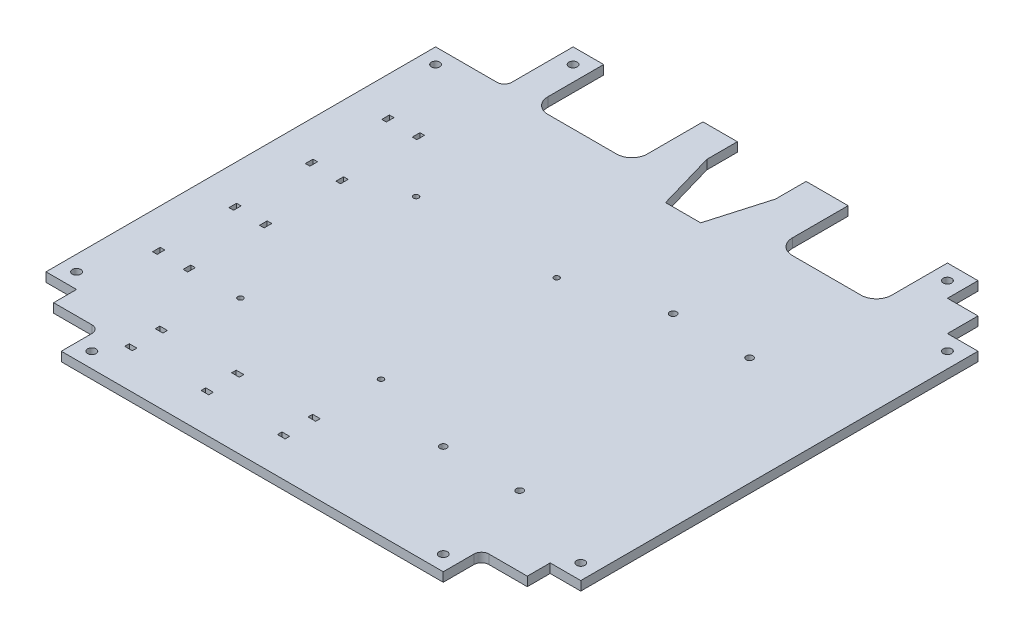
SolidWorks part; units mm, degrees
material "ABS PC"
ref_plane "Front Plane" through (0, 0, 0) normal (0, 0, 1) x (1, 0, 0)
ref_plane "Top Plane" through (0, 0, 0) normal (0, 1, 0) x (1, 0, 0)
ref_plane "Right Plane" through (0, 0, 0) normal (1, 0, 0) x (0, 0, -1)
sketch "Sketch1" plane through (0, 0, 0) normal (0, 1, 0) x (1, 0, 0)
  line L1 (-175, -170) -> (175, -170)
  line L2 (-175, -170) -> (-175, 170)
  line L3 (-175, 170) -> (175, 170)
  line L4 (175, -170) -> (175, 170)
  line L5 (-175, -170) -> (175, 170) construction
  line L6 (-175, 170) -> (175, -170) construction
  point P0 (0, 0)
  dimension "D1" = 350
  dimension "D2" = 340
extrude "Boss-Extrude1" add sketch "Sketch1" along normal blind 6
sketch "Sketch2" plane through (0, 6, 0) normal (0, 1, 0) x (1, 0, 0)
  line L0 (-175, -130) -> (-155, -130)
  line L1 (-175, 170) -> (-175, -170) construction
  line L2 (-155, -130) -> (-155, -150)
  line L3 (-175, -130) -> (-175, -170)
  line L4 (-175, -170) -> (-135, -170)
  line L5 (-155, -150) -> (-135, -150)
  line L6 (-135, -150) -> (-135, -170)
  line L7 (-175, -170) -> (175, -170) construction
  dimension "D1" = 20
  dimension "D2" = 20
extrude "Cut-Extrude2" cut sketch "Sketch2" against normal blind 6
mirror "Mirror1" about plane through (0, 0, 0) normal (0, 0, 1) of "Cut-Extrude2"
mirror "Mirror2" about plane through (0, 0, 0) normal (1, 0, 0) of "Cut-Extrude2", "Mirror1"
sketch "Sketch3" plane through (0, 6, 0) normal (0, 1, 0) x (1, 0, 0)
  line L0 (-22.5, 170) -> (-22.5, 150)
  line L1 (135, 170) -> (-135, 170) construction
  line L2 (-22.5, 150) -> (-11.5, 112)
  line L3 (-11.5, 112) -> (11.5, 112)
  line L4 (11.5, 112) -> (22.5, 150)
  line L5 (22.5, 150) -> (22.5, 170)
  line L6 (22.5, 170) -> (-22.5, 170)
  line L7 (-175, 130) -> (-175, -130) construction
  point P9 (0, 170)
  dimension "D1" = 175
  dimension "D2" = 45
  dimension "D3" = 20
  dimension "D4" = 58
  dimension "D5" = 23
extrude "Cut-Extrude3" cut sketch "Sketch3" against normal blind 6
sketch "Sketch4" plane through (0, 6, 0) normal (0, 1, 0) x (1, 0, 0)
  line L1 (-102.5, 124) -> (-92.5, 124)
  line L2 (-102.5, 124) -> (-102.5, 206.257)
  line L3 (-102.5, 206.257) -> (-92.5, 206.257)
  line L4 (-92.5, 124) -> (-92.5, 206.257)
  line L5 (-102.5, 124) -> (-92.5, 206.257) construction
  line L6 (-102.5, 206.257) -> (-92.5, 124) construction
  line L7 (92.5, 124) -> (102.5, 124)
  line L8 (92.5, 124) -> (92.5, 206.257)
  line L9 (92.5, 206.257) -> (102.5, 206.257)
  line L10 (102.5, 124) -> (102.5, 206.257)
  line L11 (92.5, 124) -> (102.5, 206.257) construction
  line L12 (92.5, 206.257) -> (102.5, 124) construction
  line L13 (-11.5, 112) -> (11.5, 112) construction
  line L14 (-22.5, 170) -> (-135, 170) construction
  point P0 (-97.5, 165.1285)
  point P5 (97.5, 165.1285)
  point P15 (0, 112)
  dimension "D1" = 195
  dimension "D2" = 97.5
  dimension "D3" = 46
  dimension "D4" = 10
extrude "Cut-Extrude4" cut sketch "Sketch4" against normal blind 6
sketch "Sketch5" plane through (0, 6, 0) normal (0, 1, 0) x (1, 0, 0)
  line L2 (-135, -170) -> (135, -170) construction
  line L3 (175, -130) -> (175, 130) construction
  line L4 (-175, 130) -> (-175, -130) construction
  circle A0 centre (104, 51.5) radius 2.25
  circle A1 centre (104, -99) radius 2.25
  circle A2 centre (54, -99) radius 2.25
  circle A3 centre (54, 51.5) radius 2.25
  circle A4 centre (-4.5, 33.75) radius 1.75
  circle A5 centre (-4.5, -81.25) radius 1.75
  circle A6 centre (-96.5, -81.25) radius 1.75
  circle A7 centre (-96.5, 33.75) radius 1.75
  dimension "D5" = 4.5
  dimension "D9" = 3.5
  dimension "D4" = 71
  dimension "D12" = 17.75
  dimension "D1" = 50
  dimension "D2" = 150.5
  dimension "D3" = 71
  dimension "D6" = 115
  dimension "D7" = 78.5
  dimension "D8" = 58.5
  dimension "D10" = 92
  dimension "D11" = 17.75
extrude "Cut-Extrude5" cut sketch "Sketch5" against normal blind 6
sketch "Sketch6" plane through (0, 6, 0) normal (0, 1, 0) x (1, 0, 0)
  line L0 (-22.5, 170) -> (-92.5, 170) construction
  line L1 (-103.5, 141) -> (-91.5, 141)
  line L2 (-103.5, 141) -> (-103.5, 150)
  line L3 (-103.5, 150) -> (-91.5, 150)
  line L4 (-91.5, 141) -> (-91.5, 150)
  line L5 (-103.5, 141) -> (-91.5, 150) construction
  line L6 (-103.5, 150) -> (-91.5, 141) construction
  line L7 (103.5, 150) -> (91.5, 150)
  line L8 (103.5, 150) -> (103.5, 141)
  line L9 (103.5, 141) -> (91.5, 141)
  line L10 (91.5, 150) -> (91.5, 141)
  line L11 (103.5, 150) -> (91.5, 141) construction
  line L12 (103.5, 141) -> (91.5, 150) construction
  line L13 (-11.5, 112) -> (11.5, 112) construction
  point P0 (-97.5, 145.5)
  point P5 (97.5, 145.5)
  point P14 (0, 112)
  dimension "D1" = 12
  dimension "D2" = 9
  dimension "D3" = 20
  dimension "D4" = 195
  dimension "D5" = 97.5
extrude "Cut-Extrude6" cut sketch "Sketch6" against normal blind 6
sketch "Sketch8" plane through (0, 6, 0) normal (0, 1, 0) x (1, 0, 0)
  line L0 (-135, -170) -> (135, -170) construction
  line L1 (-7, -126.5) -> (-2, -126.5)
  line L2 (-7, -126.5) -> (-7, -123.5)
  line L3 (-7, -123.5) -> (-2, -123.5)
  line L4 (-2, -126.5) -> (-2, -123.5)
  line L5 (-7, -126.5) -> (-2, -123.5) construction
  line L6 (-7, -123.5) -> (-2, -126.5) construction
  line L7 (-7, -146.5) -> (-2, -146.5)
  line L8 (-7, -146.5) -> (-7, -143.5)
  line L9 (-7, -143.5) -> (-2, -143.5)
  line L10 (-2, -146.5) -> (-2, -143.5)
  line L11 (-7, -146.5) -> (-2, -143.5) construction
  line L12 (-7, -143.5) -> (-2, -146.5) construction
  circle A2 centre (-4.5, -81.25) radius 1.75 construction
  point P0 (-4.5, -125)
  point P5 (-4.5, -145)
  dimension "D1" = 20
  dimension "D2" = 3
  dimension "D3" = 5
  dimension "D4" = 25
  dimension "D5" = 0
extrude "Cut-Extrude7" cut sketch "Sketch8" against normal blind 6
pattern_linear "LPattern1" count 3 spacing 50 along (-1, 0, 0) of "Cut-Extrude7"
sketch "Sketch9" plane through (0, 6, 0) normal (0, 1, 0) x (1, 0, 0)
  line L5 (-175, 130) -> (-175, -130) construction
  line L15 (-151.5, -83.75) -> (-148.5, -83.75)
  line L16 (-151.5, -83.75) -> (-151.5, -78.75)
  line L17 (-151.5, -78.75) -> (-148.5, -78.75)
  line L18 (-148.5, -83.75) -> (-148.5, -78.75)
  line L19 (-151.5, -83.75) -> (-148.5, -78.75) construction
  line L20 (-151.5, -78.75) -> (-148.5, -83.75) construction
  line L21 (-131.5, -83.75) -> (-128.5, -83.75)
  line L22 (-131.5, -83.75) -> (-131.5, -78.75)
  line L23 (-131.5, -78.75) -> (-128.5, -78.75)
  line L24 (-128.5, -83.75) -> (-128.5, -78.75)
  line L25 (-131.5, -83.75) -> (-128.5, -78.75) construction
  line L26 (-131.5, -78.75) -> (-128.5, -83.75) construction
  circle A0 centre (-96.5, -81.25) radius 1.75 construction
  point P10 (-130, -81.25)
  point P16 (-150, -81.25)
  dimension "D1" = 25
  dimension "D2" = 0
  dimension "D4" = 5
  dimension "D5" = 3
  dimension "D6" = 20
extrude "Cut-Extrude8" cut sketch "Sketch9" against normal blind 6
pattern_linear "LPattern2" count 4 spacing 50 along (0, 0, -1) of "Cut-Extrude8"
sketch "Sketch10" plane through (0, 6, 0) normal (0, 1, 0) x (1, 0, 0)
  line L0 (-135, -170) -> (135, -170) construction
  line L1 (125, -170) -> (155, -170)
  line L2 (125, -170) -> (125, -145)
  line L3 (125, -145) -> (155, -145)
  line L4 (155, -170) -> (155, -145)
  line L5 (155, -150) -> (155, -130) construction
  dimension "D1" = 30
  dimension "D2" = 25
extrude "Cut-Extrude9" cut sketch "Sketch10" against normal blind 6
mirror "Mirror3" about plane through (0, 0, 0) normal (1, 0, 0) of "Cut-Extrude9"
sketch "Sketch11" plane through (0, 6, 0) normal (0, 1, 0) x (1, 0, 0)
  line L0 (92.5, 170) -> (22.5, 170) construction
  line L1 (50, 191.4966) -> (60, 191.4966)
  line L2 (50, 191.4966) -> (50, 140)
  line L3 (50, 140) -> (60, 140)
  line L4 (60, 191.4966) -> (60, 140)
  line L5 (50, 191.4966) -> (60, 140) construction
  line L6 (50, 140) -> (60, 191.4966) construction
  line L7 (175, -130) -> (175, 130) construction
  point P0 (55, 165.7483)
  dimension "D1" = 30
  dimension "D2" = 10
  dimension "D3" = 120
extrude "Cut-Extrude10" cut sketch "Sketch11" against normal blind 6
sketch "Sketch12" plane through (0, 6, 0) normal (0, 1, 0) x (1, 0, 0)
  line L0 (-175, 130) -> (-175, -130) construction
  line L1 (-130, 125) -> (-175, 125)
  line L2 (-130, 125) -> (-130, 170)
  line L3 (-130, 170) -> (-175, 170)
  line L4 (-175, 125) -> (-175, 170)
  line L5 (-102.5, 170) -> (-135, 170) construction
  dimension "D1" = 0
  dimension "D2" = 0
  dimension "D3" = 45
  dimension "D4" = 45
extrude "Cut-Extrude11" cut sketch "Sketch12" against normal blind 6
fillet "Fillet2" radius 4.9 5 edges at (-125, 3, 145) (125, 3, 145) (50, 3, -140) (60, 3, -140) (-130, 3, -125)
sketch "Sketch13" plane through (0, 6, 0) normal (0, 1, 0) x (1, 0, 0)
  line L0 (-125, -170) -> (125, -170) construction
  line L1 (-125, -149.9) -> (-125, -170) construction
  line L2 (125, -149.9) -> (125, -170) construction
  line L3 (155, -130) -> (175, -130) construction
  line L4 (175, -130) -> (175, 130) construction
  line L5 (-155, -130) -> (-175, -130) construction
  line L6 (-175, 125) -> (-175, -130) construction
  line L7 (-175, 125) -> (-134.9, 125) construction
  line L8 (-130, 129.9) -> (-130, 170) construction
  line L9 (-102.5, 170) -> (-130, 170) construction
  line L10 (135, 170) -> (102.5, 170) construction
  line L11 (135, 170) -> (135, 150) construction
  line L12 (155, 130) -> (175, 130) construction
  circle A0 centre (165, -120) radius 2.75
  circle A1 centre (165, 120) radius 2.75
  circle A2 centre (125, 160) radius 2.75
  circle A3 centre (-120, 160) radius 2.75
  circle A4 centre (-165, 115) radius 2.75
  circle A5 centre (-165, -120) radius 2.75
  circle A6 centre (-115, -160) radius 2.75
  circle A7 centre (115, -160) radius 2.75
  dimension "D2" = 10
  dimension "D3" = 10
  dimension "D4" = 10
  dimension "D5" = 10
  dimension "D6" = 10
  dimension "D7" = 10
  dimension "D8" = 10
  dimension "D9" = 5.5
  dimension "D10" = 10
  dimension "D11" = 10
  dimension "D12" = 10
  dimension "D13" = 10
  dimension "D14" = 10
  dimension "D15" = 10
  dimension "D16" = 10
  dimension "D17" = 10
  dimension "D1" = 10
extrude "Cut-Extrude12" cut sketch "Sketch13" against normal blind 6
sketch "Sketch14" plane through (0, 6, 0) normal (0, 1, 0) x (1, 0, 0)
  line L0 (-22.5, 170) -> (-92.5, 170) construction
  line L1 (-107.5, 150) -> (-67.5, 150)
  line L2 (-107.5, 150) -> (-107.5, 170)
  line L3 (-107.5, 170) -> (-67.5, 170)
  line L4 (-67.5, 150) -> (-67.5, 170)
  line L5 (-107.5, 150) -> (-67.5, 170) construction
  line L6 (-107.5, 170) -> (-67.5, 150) construction
  line L7 (135, 170) -> (102.5, 170) construction
  line L8 (57.5, 150) -> (107.5, 150)
  line L9 (57.5, 150) -> (57.5, 170)
  line L10 (57.5, 170) -> (107.5, 170)
  line L11 (107.5, 150) -> (107.5, 170)
  line L12 (57.5, 150) -> (107.5, 170) construction
  line L13 (57.5, 170) -> (107.5, 150) construction
  line L14 (-103.5, 145.5) -> (-91.5, 145.5) construction
  line L15 (-103.5, 150) -> (-103.5, 141) construction
  line L16 (-91.5, 141) -> (-91.5, 150) construction
  line L17 (91.5, 145.5) -> (103.5, 145.5)
  line L18 (91.5, 150) -> (91.5, 141) construction
  line L19 (103.5, 141) -> (103.5, 150) construction
  point P0 (-87.5, 160)
  point P7 (82.5, 160)
  point P14 (-97.5, 145.5)
  point P23 (97.5, 145.5)
  dimension "D1" = 40
  dimension "D2" = 20
  dimension "D3" = 10
  dimension "D4" = 10
  dimension "D5" = 50
extrude "Cut-Extrude13" cut sketch "Sketch14" against normal blind 10 contours L8 L11 L10 L9 | L1 L4 L3 L2 region at (-87.5, 6, -160) region at (82.5, 6, -160)
fillet "Fillet4" 2 edges at (-102.5, 3, -124) (-92.5, 3, -124) type full round first side face at (-102.5, 3, -132.5) second side face at (-92.5, 3, -132.5) middle face at (-97.5, 3, -124)
fillet "Fillet5" 2 edges at (92.5, 3, -124) (102.5, 3, -124) type full round first side face at (92.5, 3, -132.5) second side face at (102.5, 3, -132.5) middle face at (97.5, 3, -124)
sketch "Sketch15" plane through (0, 0, 0) normal (0, -1, 0) x (-1, 0, 0)
  line L0 (110, 170) -> (110, 123.4843)
  line L1 (107.5, 170) -> (130, 170) construction
  line L2 (110, 123.4843) -> (45, 123.4843)
  line L3 (-50, 123.4843) -> (-115, 123.4843)
  line L4 (-115, 123.4843) -> (-115, 170)
  line L5 (-135, 170) -> (-107.5, 170) construction
  line L6 (-115, 170) -> (-50, 170)
  line L7 (-135, 170) -> (-135, 150) construction
  line L8 (-50, 170) -> (-50, 123.4843)
  line L9 (45, 123.4843) -> (45, 170)
  line L10 (130, 129.9) -> (130, 170) construction
  line L11 (45, 170) -> (110, 170)
  dimension "D1" = 20
  dimension "D2" = 65
  dimension "D3" = 20
extrude "Cut-Extrude14" cut sketch "Sketch15" against normal blind 10
fillet "Fillet6" radius 10 4 edges at (-45, 3, -123.4843) (-110, 3, -123.4843) (50, 3, -123.4843) (115, 3, -123.4843)
equation "\"D2@Sketch4\"=\"D1@Sketch4\"/2"
equation "\"D5@Sketch6\"=\"D4@Sketch6\"/2"
